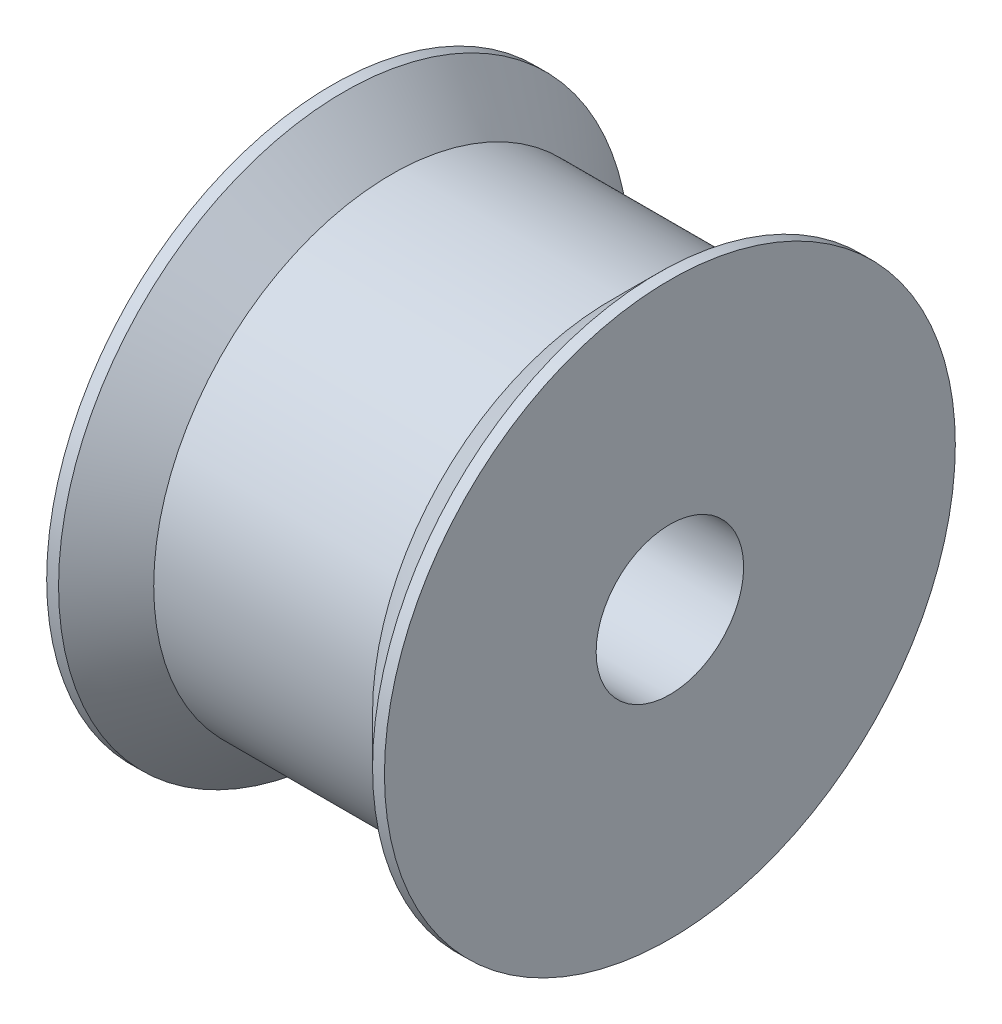
SolidWorks part; units mm, degrees
ref_plane "Front Plane" through (0, 0, 0) normal (0, 0, 1) x (1, 0, 0)
ref_plane "Top Plane" through (0, 0, 0) normal (0, 1, 0) x (1, 0, 0)
ref_plane "Right Plane" through (0, 0, 0) normal (1, 0, 0) x (0, 0, -1)
sketch "Sketch2" plane through (0, 0, 0) normal (0, 1, 0) x (1, 0, 0)
  line L0 (-7.1, 12) -> (-6.6, 12)
  line L1 (-6.6, 12) -> (-4.6, 10)
  line L2 (-4.6, 10) -> (4.6, 10)
  line L3 (4.6, 10) -> (6.6, 12)
  line L4 (6.6, 12) -> (7.1, 12)
  line L5 (7.1, 12) -> (7.1, 0)
  line L6 (-7.1, 12) -> (-7.1, 0)
  line L7 (-54.6936, 0) -> (47.2254, 0) construction
  line L8 (0, -23.2469) -> (0, 34.557) construction
  line L9 (7.1, 0) -> (-7.1, 0)
  point P16 (0, 10)
  dimension "D1" = 12
  dimension "D2" = 2.5
  dimension "D3" = 9.2
  dimension "D4" = 10
revolve "Revolve1" add sketch "Sketch2" angle 360 about L9
sketch "Sketch3" plane through (-7.1, 0, 0) normal (-1, 0, 0) x (0, 0, 1)
  circle A0 centre (0, 0) radius 3.1
  dimension "D1" = 6.2
extrude "Cut-Extrude1" cut sketch "Sketch3" against normal up to surface (14.2 mm away) up to face at (7.1, 0, -12)
